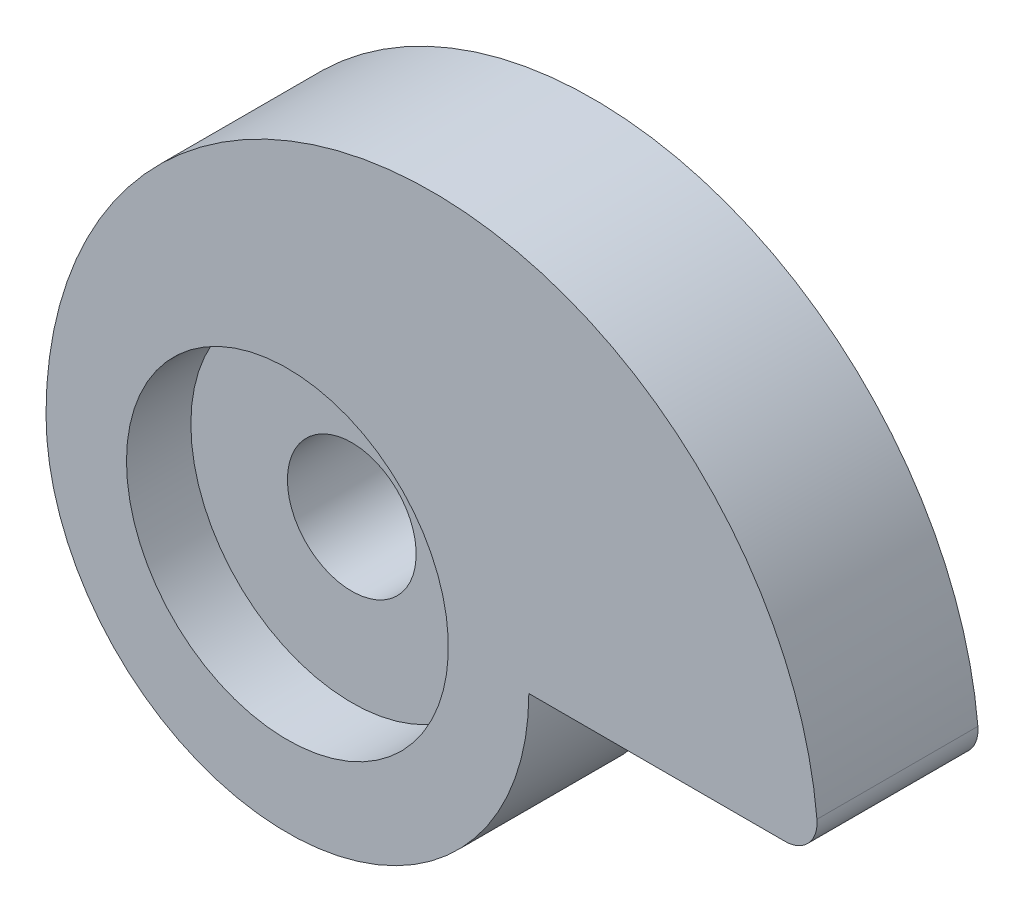
SolidWorks part; units mm, degrees
ref_plane "Front Plane" through (0, 0, 0) normal (0, 0, 1) x (1, 0, 0)
ref_plane "Top Plane" through (0, 0, 0) normal (0, 1, 0) x (1, 0, 0)
ref_plane "Right Plane" through (0, 0, 0) normal (1, 0, 0) x (0, 0, -1)
sketch "Sketch1" plane through (0, 0, 0) normal (0, 0, 1) x (1, 0, 0)
  line L0 (-12, 0) -> (12, 0) construction
  line L2 (3, 0) -> (12, 0)
  arc A0 (12, 0) -> (-12, 0) centre (0, 0) ccw
  circle A3 centre (-4.5, 0) radius 2
  arc A4 (-12, 0) -> (3, 0) centre (-4.5, 0) ccw
  dimension "D1" = 24
  dimension "D2" = 4
  dimension "D3" = 7.5
extrude "Boss-Extrude1" add sketch "Sketch1" along normal blind 5
sketch "Sketch3" plane through (0, 0, 0) normal (0, 0, 1) x (1, 0, 0)
  circle A0 centre (-4.5, 0) radius 5
  circle A1 centre (-4.5, 0) radius 2 construction
  circle A2 centre (-4.5, 0) radius 2
  dimension "D1" = 10
extrude "Boss-Extrude2" add sketch "Sketch3" against normal blind 5
sketch "Sketch4" plane through (0, 0, -5) normal (0, 0, -1) x (-1, 0, 0)
  line L1 (-2.0014, -1) -> (11.0014, -1)
  line L2 (-2.0014, -1) -> (-2.0014, 1)
  line L3 (-2.0014, 1) -> (11.0014, 1)
  line L4 (11.0014, -1) -> (11.0014, 1)
  line L5 (-2.0014, -1) -> (11.0014, 1) construction
  line L6 (-2.0014, 1) -> (11.0014, -1) construction
  point P0 (4.5, 0)
  dimension "D1" = 2
extrude "Cut-Extrude1" cut sketch "Sketch4" against normal blind 3
fillet "Fillet1" radius 1 4 edges at (-7.8155, 1, -2) (-7.8155, -1, -2) (-1.1845, -1, -2) (-1.1845, 1, -2)
sketch "Sketch5" plane through (0, 0, 5) normal (0, 0, -1) x (-1, 0, 0)
  circle A1 centre (4.5, 0) radius 5
  circle A2 centre (4.5, 0) radius 2 construction
  dimension "D1" = 10
extrude "Cut-Extrude2" cut sketch "Sketch5" along normal blind 2
fillet "Fillet2" radius 1.5 1 edges at (0.5, 0, 0)
fillet "Fillet3" radius 1 1 edges at (12, 0, 2.5)
